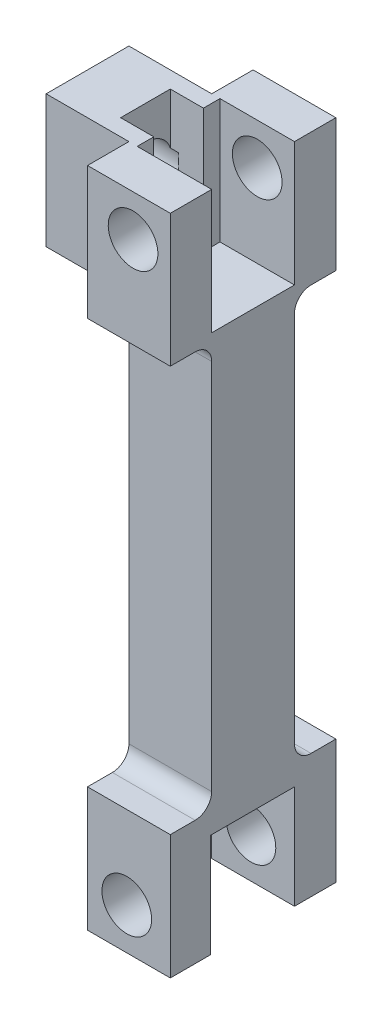
SolidWorks part; units mm, degrees
ref_plane "Front" through (0, 0, 0) normal (0, 0, 1) x (1, 0, 0)
ref_plane "Top" through (0, 0, 0) normal (0, 1, 0) x (1, 0, 0)
ref_plane "Right" through (0, 0, 0) normal (1, 0, 0) x (0, 0, -1)
sketch "Sketch1" plane through (0, 0, 0) normal (0, 0, 1) x (1, 0, 0)
  line L0 (-4.5761, -135.7066) -> (-29.9761, -135.7066)
  line L1 (-29.9761, 67.4934) -> (-4.5761, 67.4934)
  line L2 (-29.9761, 26.8534) -> (-29.9761, -135.7066)
  line L4 (-4.5761, 67.4934) -> (-4.5761, -135.7066)
  line L5 (-29.9761, 67.4934) -> (-55.3761, 67.4934)
  line L7 (-29.9761, 26.8534) -> (-55.3761, 26.8534)
  line L8 (-55.3761, 67.4934) -> (-55.3761, 26.8534)
  dimension "D1" = 25.4
  dimension "D2" = 203.2
  dimension "D3" = 25.4
  dimension "D4" = 40.64
extrude "Base-Extrude" add sketch "Sketch1" against normal blind 25.4
sketch "Sketch7" plane through (-29.9761, 0, 0) normal (-1, 0, 0) x (0, 0, 1)
  line L0 (0, 26.8534) -> (0, -135.7066) construction
  line L1 (-38.1, -135.7066) -> (-25.4, -135.7066)
  line L2 (-38.1, -135.7066) -> (-38.1, -97.6066)
  line L3 (-38.1, -97.6066) -> (-25.4, -97.6066)
  line L4 (12.7, -135.7066) -> (12.7, -97.6066)
  line L5 (-25.4, 26.8534) -> (-25.4, -135.7066) construction
  line L6 (0, -135.7066) -> (0, -97.6066)
  line L7 (-25.4, -135.7066) -> (-25.4, -97.6066)
  line L8 (0, -97.6066) -> (12.7, -97.6066)
  line L9 (0, -135.7066) -> (12.7, -135.7066)
  dimension "D1" = 12.7
  dimension "D2" = 12.7
  dimension "D3" = 38.1
extrude "Boss-Extrude5" add sketch "Sketch7" against normal blind 25.4
sketch "Sketch8" plane through (-29.9761, 0, 0) normal (-1, 0, 0) x (0, 0, 1)
  line L0 (-38.1, -135.7066) -> (12.7, -135.7066) construction
  line L1 (0.3517, -135.7066) -> (0.3517, -103.9566)
  line L2 (0.3517, -103.9566) -> (-25.4, -103.9566)
  line L3 (-25.4, -135.7066) -> (0.3517, -135.7066)
  line L4 (-25.4, -103.9566) -> (-25.4, -135.7066)
  dimension "D1" = 31.75
extrude "Cut-Extrude5" cut sketch "Sketch8" against normal up to vertex (25.4 mm away) up to point (-4.5761, -135.7066, -38.1)
sketch "Sketch11" plane through (-4.5761, 0, 0) normal (1, 0, 0) x (0, 0, -1)
  line L0 (25.4, 67.4934) -> (25.4, 26.8534)
  line L1 (-12.7, 67.4934) -> (0, 67.4934)
  line L2 (-12.7, 67.4934) -> (-12.7, 26.8534)
  line L3 (-12.7, 26.8534) -> (0, 26.8534)
  line L4 (38.1, 67.4934) -> (38.1, 26.8534)
  line L5 (0, 67.4934) -> (0, 26.8534)
  line L6 (25.4, 26.8534) -> (38.1, 26.8534)
  line L7 (25.4, 67.4934) -> (38.1, 67.4934)
  dimension "D1" = 12.7
  dimension "D2" = 12.7
  dimension "D3" = 40.64
extrude "Boss-Extrude6" add sketch "Sketch11" against normal up to vertex (25.4 mm away) up to point (-29.9761, 26.8534, -25.4)
sketch "Sketch12" plane through (-4.5761, 0, 0) normal (1, 0, 0) x (0, 0, -1)
  line L0 (38.1, 67.4934) -> (-12.7, 67.4934) construction
  line L1 (0, 67.4934) -> (25.4, 67.4934)
  line L2 (0, 67.4934) -> (0, 29.3934)
  line L3 (0, 29.3934) -> (25.4, 29.3934)
  line L4 (25.4, 67.4934) -> (25.4, 29.3934)
  dimension "D1" = 38.1
extrude "Cut-Extrude7" cut sketch "Sketch12" against normal blind 22.86
sketch "Sketch13" plane through (-55.3761, 0, 0) normal (-1, 0, 0) x (0, 0, 1)
  circle A0 centre (-13.0885, 49.4298) radius 7.62
extrude "Cut-Extrude8" cut sketch "Sketch13" against normal blind 20.32
sketch "Sketch14" plane through (0, 0, -38.1) normal (0, 0, -1) x (-1, 0, 0)
  line L1 (29.9761, 67.4934) -> (4.5761, 67.4934) construction
  line L2 (4.5761, -135.7066) -> (29.9761, -135.7066) construction
  line L4 (4.5761, -103.9566) -> (4.5761, -135.7066) construction
  circle A0 centre (16.0061, 54.7934) radius 7.62
  circle A1 centre (17.9313, -123.0066) radius 7.62
  point P14 (4.5761, -119.8316)
  dimension "D1" = 12.7
  dimension "D2" = 12.7
  dimension "D3" = 11.43
  dimension "D4" = 13.7274
extrude "Cut-Extrude9" cut sketch "Sketch14" against normal up to vertex (50.8 mm away) up to point (-4.5761, 26.8534, 12.7)
sketch "Sketch15" plane through (0, 67.4934, 0) normal (0, 1, 0) x (1, 0, 0)
  line L0 (-27.4361, 25.4) -> (-27.4361, 0) construction
  line L1 (-17.2761, 20.32) -> (-37.5961, 20.32)
  line L2 (-17.2761, 20.32) -> (-17.2761, 5.08)
  line L3 (-17.2761, 5.08) -> (-37.5961, 5.08)
  line L4 (-37.5961, 20.32) -> (-37.5961, 5.08)
  line L5 (-17.2761, 20.32) -> (-37.5961, 5.08) construction
  line L6 (-17.2761, 5.08) -> (-37.5961, 20.32) construction
  point P0 (-27.4361, 12.7)
  dimension "D1" = 15.24
  dimension "D2" = 10.16
extrude "Cut-Extrude10" cut sketch "Sketch15" against normal up to surface (38.1 mm away) up to face at (-16.0061, 29.3934, -12.7)
fillet "Fillet1" radius 5.08 4 edges at (-17.2761, 26.8534, 0) (-17.2761, 26.8534, -25.4)
